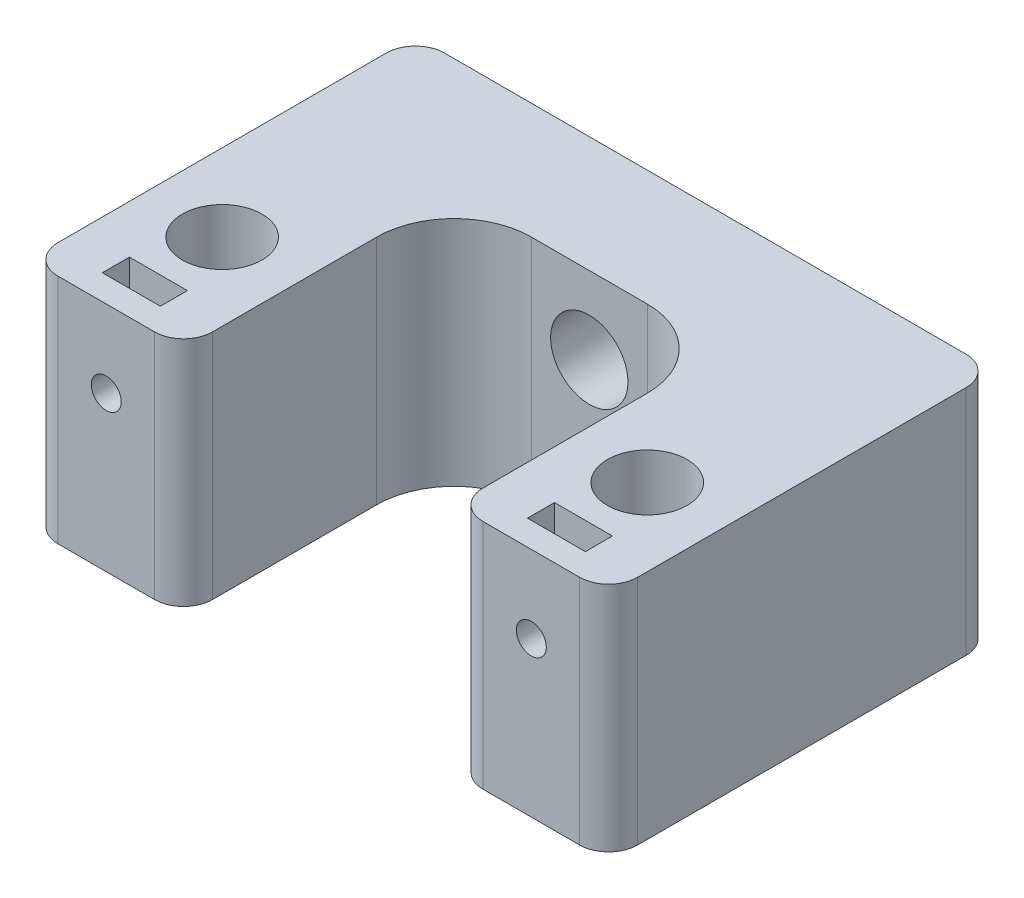
SolidWorks part; units mm, degrees
ref_plane "Front Plane" through (0, 0, 0) normal (0, 0, 1) x (1, 0, 0)
ref_plane "Top Plane" through (0, 0, 0) normal (0, 1, 0) x (1, 0, 0)
ref_plane "Right Plane" through (0, 0, 0) normal (1, 0, 0) x (0, 0, -1)
sketch "Sketch1" plane through (0, 0, 0) normal (0, 1, 0) x (1, 0, 0)
  line L0 (0, 28) -> (0, -8) construction
  line L1 (-30, 28) -> (30, 28)
  line L2 (-30, 28) -> (-30, -28)
  line L3 (-14, -15.7797) -> (-14, 16)
  line L4 (30, 28) -> (30, -28)
  line L5 (-30, 28) -> (30, -28) construction
  line L6 (-30, -28) -> (30, 28) construction
  line L8 (-30, -28) -> (-30, -12)
  line L9 (-30, -12) -> (-14, -12)
  line L10 (-14, -15.7797) -> (-14, -12)
  line L11 (14, -15.7797) -> (14, -12)
  line L12 (30, -12) -> (14, -12)
  line L13 (30, -28) -> (30, -12)
  line L14 (-14, 16) -> (14, 16)
  line L15 (14, 16) -> (14, -15.7797)
  circle A0 centre (-22, 0) radius 4.125
  circle A1 centre (22, 0) radius 4.125
  point P4 (0, 0)
  dimension "D1" = 8.25
  dimension "D2" = 44
  dimension "D3" = 22
  dimension "D4" = 12
  dimension "D5" = 8
  dimension "D6" = 28
  dimension "D7" = 12
extrude "Boss-Extrude1" add sketch "Sketch1" along normal blind 24 contours L10 L8 L9 | L4 L1 L2 A1 A0 | L13 L11 L12 region at (0, 0, -27.2789)
sketch "Sketch2" plane through (0, 24, 0) normal (0, 1, 0) x (1, 0, 0)
  line L1 (-25, -6.6) -> (-19, -6.6)
  line L2 (-25, -6.6) -> (-25, -9.4)
  line L3 (-25, -9.4) -> (-19, -9.4)
  line L4 (-19, -6.6) -> (-19, -9.4)
  line L5 (-25, -6.6) -> (-19, -9.4) construction
  line L6 (-25, -9.4) -> (-19, -6.6) construction
  point P0 (-22, -8)
  point P7 (-22, 0)
  dimension "D1" = 2.8
  dimension "D2" = 6
  dimension "D3" = 8
extrude "Cut-Extrude1" cut sketch "Sketch2" against normal through all
sketch "Sketch3" plane through (0, 0, 12) normal (0, 0, 1) x (1, 0, 0)
  line L0 (-30, 24) -> (-14, 24) construction
  line L1 (-30, 24) -> (-30, 0) construction
  circle A0 centre (-22, 16) radius 1.55
  dimension "D1" = 3.1
  dimension "D2" = 8
  dimension "D3" = 8
extrude "Cut-Extrude2" cut sketch "Sketch3" against normal blind 10
mirror "Mirror1" about plane through (0, 0, 0) normal (1, 0, 0) of "Cut-Extrude1", "Cut-Extrude2"
fillet "Fillet1" radius 8 2 edges at (14, 12, -16) (-14, 12, -16)
fillet "Fillet2" radius 3 6 edges at (-30, 12, -28) (30, 12, -28) (30, 12, 12) (14, 12, 12) (-30, 12, 12) (-14, 12, 12)
sketch "Sketch4" plane through (0, 0, -16) normal (0, 0, 1) x (1, 0, 0)
  line L0 (-27, 24) -> (27, 24) construction
  circle A0 centre (0, 16) radius 4
  point P2 (0, 24)
  dimension "D2" = 8
  dimension "D1" = 8
extrude "Cut-Extrude3" cut sketch "Sketch4" against normal through all
